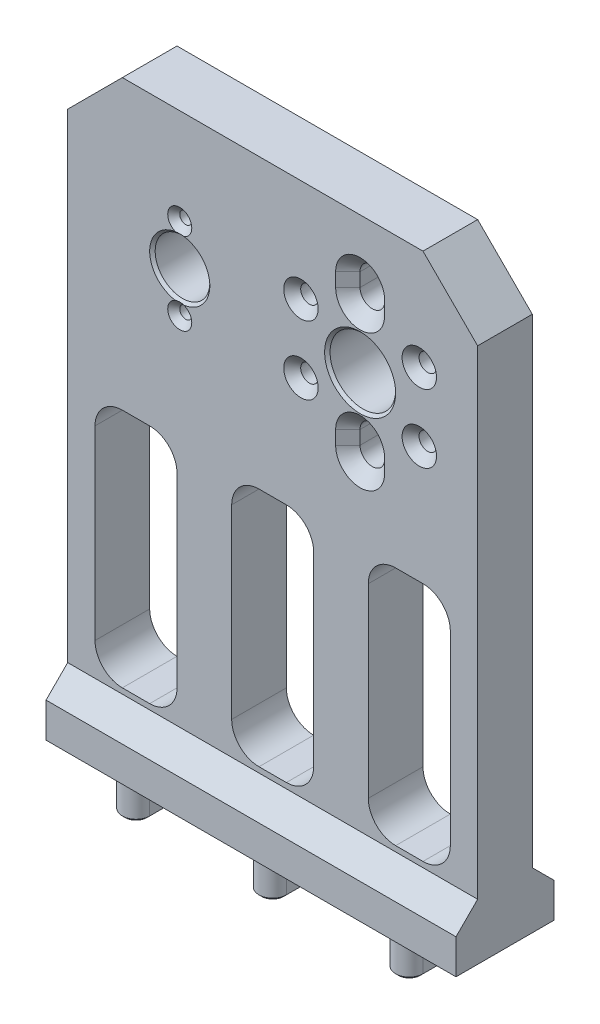
SolidWorks part; units mm, degrees
material "6061 Сплав"
ref_plane "Front Plane" through (0, 0, 0) normal (0, 0, 1) x (1, 0, 0)
ref_plane "Top Plane" through (0, 0, 0) normal (0, 1, 0) x (1, 0, 0)
ref_plane "Right Plane" through (0, 0, 0) normal (1, 0, 0) x (0, 0, -1)
sketch "Sketch1" plane through (0, 0, 0) normal (0, 0, 1) x (1, 0, 0)
  line L0 (59.2007, -25) -> (-71.3111, -25) construction
  line L1 (-37.5, -108) -> (37.5, -108)
  line L2 (-37.5, 0) -> (-37.5, -108)
  line L3 (-37.5, 0) -> (37.5, 0)
  line L4 (37.5, -108) -> (37.5, 0)
  point P6 (0, 0)
  dimension "D1" = 83
  dimension "D2" = 75
  dimension "D3" = 108
extrude "Boss-Extrude1" add sketch "Sketch1" along normal blind 10
sketch "Sketch2" plane through (0, 0, 0) normal (0, 0, 1) x (1, 0, 0)
  line L0 (-37.5, -108) -> (37.5, -108) construction
  line L1 (16, -25) -> (-37.0724, -25) construction
  line L2 (0, 0) -> (0, 29.3343) construction
  line L3 (0, 0) -> (0, -25) construction
  circle A0 centre (16, -25) radius 6
  circle A1 centre (-17, -25) radius 5
  point P2 (0, -108)
  point P7 (0, -25)
  dimension "D1" = 83
  dimension "D2" = 16
  dimension "D3" = 17
extrude "Cut-Extrude2" cut sketch "Sketch2" along normal through all
sketch "Sketch9" plane through (0, 0, 10) normal (0, 0, 1) x (1, 0, 0)
  line L1 (5.1747, -31.25) -> (26.8253, -31.25) construction
  line L2 (5.1747, -31.25) -> (5.1747, -18.75) construction
  line L3 (5.1747, -18.75) -> (26.8253, -18.75) construction
  line L4 (26.8253, -31.25) -> (26.8253, -18.75) construction
  line L5 (5.1747, -31.25) -> (26.8253, -18.75) construction
  line L6 (5.1747, -18.75) -> (26.8253, -31.25) construction
  point P0 (16, -25)
  point P7 (5.1747, -18.75)
  point P8 (26.8253, -18.75)
  point P9 (26.8253, -31.25)
  point P10 (5.1747, -31.25)
  dimension "D1" = 60
hole_wizard "Зенковка для  винта с плоской головкой M31" positions "Sketch11" profile "Sketch10" countersink size "M3" standard "Ansi Metric" end condition through all
sketch "Sketch11" plane through (0, 0, 10) normal (0, 0, 1) x (1, 0, 0)
  point P0 (26.8253, -18.75)
  point P3 (5.1747, -18.75)
  point P6 (5.1747, -31.25)
  point P9 (26.8253, -31.25)
sketch "Sketch10" plane through (26.8253, -18.75, 10) normal (1, 0, 0) x (0, -1, 0)
  line L0 (0, 0) -> (0, 10)
  line L1 (0, 10) -> (1.6, 10)
  line L2 (1.6, 10) -> (1.6, 1.55)
  line L3 (1.6, 1.55) -> (3.15, 0)
  line L5 (3.15, 0) -> (0, 0)
  line L6 (-1.6, 1.55) -> (-3.15, 0) construction
  line L11 (0, -6.35) -> (0, 107.95) construction
  dimension "Thru Hole Dia." = 3.2
  dimension "Thru Hole Depth" = 10
  dimension "Near C'Sink Dia." = 6.3
  dimension "Near C'Sink Angle" = 90
sketch "Sketch13" plane through (37.5, 0, 0) normal (1, 0, 0) x (0, 0, -1)
  line L1 (-10, -108) -> (-10, 0) construction
  line L2 (-10, -97.69) -> (-13.96, -101.65)
  line L3 (-13.96, -101.65) -> (-13.96, -108)
  line L4 (-13.96, -108) -> (-10, -108)
  line L5 (0, -108) -> (0, 0) construction
  line L8 (-10, -97.69) -> (0, -97.69)
  line L10 (3.96, -108) -> (0, -108)
  line L11 (3.96, -101.65) -> (3.96, -108)
  line L12 (0, -97.69) -> (3.96, -101.65)
  line L13 (-10, -108) -> (0, -108)
  point P1 (0, -97.69)
  dimension "D1" = 6.35
  dimension "D2" = 3.96
  dimension "D3" = 3.96
  dimension "D4" = 45
extrude "Boss-Extrude2" add sketch "Sketch13" against normal through all contours L3 L4 L13 L10 L11 L12 L8 L2
sketch "Sketch14" plane through (0, -108, 0) normal (0, -1, 0) x (1, 0, 0)
  line L0 (-37.5, -3.96) -> (37.5, -3.96) construction
  line L1 (-37.5, 13.96) -> (37.5, 13.96) construction
  line L2 (-2.5, 0) -> (-2.5, 10)
  line L3 (25, 13.96) -> (25, -3.96) construction
  line L4 (2.5, 0) -> (2.5, 10)
  line L5 (0, 13.96) -> (0, -3.96) construction
  line L6 (-2.5, 10) -> (2.5, 10) construction
  line L7 (-2.5, 0) -> (2.5, 0) construction
  line L8 (-2.5, 0) -> (2.5, 10) construction
  line L9 (-2.5, 10) -> (2.5, 0) construction
  line L10 (0, -3.96) -> (-37.5, -3.96) construction
  line L11 (22.5, 10) -> (27.5, 10) construction
  line L12 (22.5, 0) -> (22.5, 10)
  line L13 (22.5, 0) -> (27.5, 0) construction
  line L14 (27.5, 0) -> (27.5, 10)
  line L15 (22.5, 0) -> (27.5, 10) construction
  line L16 (22.5, 10) -> (27.5, 0) construction
  line L17 (-27.5, 0) -> (-27.5, 10)
  line L18 (-22.5, 0) -> (-22.5, 10)
  line L19 (-25, 13.96) -> (-25, -3.96) construction
  line L20 (-27.5, 10) -> (-22.5, 10) construction
  line L21 (-27.5, 0) -> (-22.5, 0) construction
  line L22 (25, -3.96) -> (-12.5, -3.96) construction
  line L23 (-27.5, 0) -> (-22.5, 10) construction
  line L24 (-27.5, 10) -> (-22.5, 0) construction
  line L25 (-25, -3.96) -> (-62.5, -3.96) construction
  arc A0 (-2.5, 10) -> (2.5, 10) centre (0, 10) cw
  arc A1 (2.5, 0) -> (-2.5, 0) centre (0, 0) cw
  arc A2 (22.5, 10) -> (27.5, 10) centre (25, 10) cw
  arc A3 (27.5, 0) -> (22.5, 0) centre (25, 0) cw
  arc A4 (-27.5, 10) -> (-22.5, 10) centre (-25, 10) cw
  arc A5 (-22.5, 0) -> (-27.5, 0) centre (-25, 0) cw
  point P11 (25, 5)
  point P12 (0, 5)
  point P13 (0, 13.96)
  point P14 (0, -3.96)
  point P15 (0, 5)
  point P18 (25, 13.96)
  point P19 (25, -3.96)
  point P21 (25, 5)
  point P33 (-25, 5)
  point P34 (-25, 13.96)
  point P35 (-25, -3.96)
  point P36 (-25, 5)
  dimension "D1" = 3
  dimension "D2" = 5
  dimension "D3" = 10
  dimension "D4" = 25
extrude "Boss-Extrude3" add sketch "Sketch14" along normal blind 7
chamfer "Chamfer2" distance 0.5 angle 45 12 edges at (27.5, -115, 5) (25, -115, -2.5) (22.5, -115, 5) (25, -115, 12.5) (-22.5, -115, 5) (-25, -115, -2.5) (-27.5, -115, 5) (-25, -115, 12.5) (2.5, -115, 5) (0, -115, -2.5) (-2.5, -115, 5) (0, -115, 12.5)
sketch "Sketch15" plane through (0, -108, 0) normal (0, -1, 0) x (1, 0, 0)
  line L1 (27.5, 5) -> (0, 5) construction
  line L2 (-27.5, 0) -> (-27.5, 10) construction
  line L3 (27.5, 10) -> (27.5, 0) construction
  line L4 (-37.5, 13.96) -> (-37.5, -3.96) construction
  line L9 (0, 5) -> (-27.5, 5) construction
  line L10 (-27.5, 5) -> (-37.5, 5) construction
  line L12 (27.5, 5) -> (37.5, 5) construction
  line L13 (37.5, 13.96) -> (37.5, -3.96) construction
  point P2 (13.75, 5)
  point P3 (-32.5, 5)
  point P5 (-13.75, 5)
  point P14 (32.5, 5)
sketch "Sketch19" plane through (0, 0, 10) normal (0, 0, 1) x (1, 0, 0)
  circle A0 centre (16, -25) radius 12.5 construction
  point P6 (16, -12.5)
  point P7 (16, -37.5)
  dimension "D1" = 25
hole_wizard "Зенковка для  винта с потайной головкой с внутренним шестигранником M41" positions "Sketch21" profile "Sketch20" size "M4" standard "Ansi Metric" slot yes
sketch "Sketch21" plane through (0, 0, 10) normal (0, 0, 1) x (1, 0, 0)
  line L2 (16, -9) -> (16, -16) construction
  point P0 (16, -12.5)
  point P5 (16, -37.5)
  dimension "D1" = 7
sketch "Sketch20" plane through (16, -12.5, 10) normal (1, 0, 0) x (0, -1, 0)
  line L0 (0, 0) -> (0, 16.3519)
  line L1 (0, 16.3519) -> (2.25, 15)
  line L2 (2.25, 15) -> (2.25, 2.23)
  line L3 (2.25, 2.23) -> (4.48, 0)
  line L5 (4.48, 0) -> (0, 0)
  line L6 (-2.25, 2.23) -> (-4.48, 0) construction
  line L10 (0, 16.3519) -> (-2.25, 15) construction
  line L11 (0, -6.35) -> (0, 107.95) construction
  dimension "Hole Dia." = 4.5
  dimension "Hole Depth" = 15
  dimension "Near C'Sink Dia." = 8.96
  dimension "Near C'Sink Angle" = 90
  dimension "Drill Angle" = 118
chamfer "Chamfer4" distance 0.5 angle 45 16 edges at (22, -25, 10) (6.7747, -31.25, 0) (16, -34, 0) (18.25, -37.5, 0) (13.75, -37.5, 0) (16, -41, 0) (28.4253, -31.25, 0) (28.4253, -18.75, 0) (22, -25, 0) (6.7747, -18.75, 0) (13.75, -12.5, 0) (16, -9, 0) (16, -16, 0) (18.25, -12.5, 0) (-12, -25, 10) (-12, -25, 0)
sketch "Sketch22" plane through (0, 0, 10) normal (0, 0, 1) x (1, 0, 0)
  line L0 (-37.5, -97.69) -> (37.5, -97.69) construction
  line L1 (2.5, -96.69) -> (-2.5, -96.69)
  line L2 (7.5, -91.69) -> (7.5, -57.69)
  line L3 (2.5, -52.69) -> (-2.5, -52.69)
  line L4 (-7.5, -91.69) -> (-7.5, -57.69)
  line L5 (-7.5, -74.69) -> (7.5, -74.69) construction
  line L6 (-22.5, -96.69) -> (-27.5, -96.69)
  line L7 (-17.5, -91.69) -> (-17.5, -57.69)
  line L8 (-22.5, -52.69) -> (-27.5, -52.69)
  line L9 (-32.5, -91.69) -> (-32.5, -57.69)
  line L10 (-32.5, -74.69) -> (-17.5, -74.69) construction
  line L11 (27.5, -96.69) -> (22.5, -96.69)
  line L12 (32.5, -91.69) -> (32.5, -57.69)
  line L13 (27.5, -52.69) -> (22.5, -52.69)
  line L14 (17.5, -91.69) -> (17.5, -57.69)
  line L19 (17.5, -74.69) -> (32.5, -74.69) construction
  arc A0 (-2.5, -96.69) -> (-7.5, -91.69) centre (-2.5, -91.69) cw
  arc A1 (2.5, -96.69) -> (7.5, -91.69) centre (2.5, -91.69) ccw
  arc A2 (22.5, -96.69) -> (17.5, -91.69) centre (22.5, -91.69) cw
  arc A3 (27.5, -96.69) -> (32.5, -91.69) centre (27.5, -91.69) ccw
  arc A4 (32.5, -57.69) -> (27.5, -52.69) centre (27.5, -57.69) ccw
  arc A5 (22.5, -52.69) -> (17.5, -57.69) centre (22.5, -57.69) ccw
  arc A6 (7.5, -57.69) -> (2.5, -52.69) centre (2.5, -57.69) ccw
  arc A7 (-2.5, -52.69) -> (-7.5, -57.69) centre (-2.5, -57.69) ccw
  arc A8 (-27.5, -96.69) -> (-32.5, -91.69) centre (-27.5, -91.69) cw
  arc A9 (-22.5, -96.69) -> (-17.5, -91.69) centre (-22.5, -91.69) ccw
  arc A10 (-17.5, -57.69) -> (-22.5, -52.69) centre (-22.5, -57.69) ccw
  arc A11 (-27.5, -52.69) -> (-32.5, -57.69) centre (-27.5, -57.69) ccw
  point P4 (0, -74.69)
  point P18 (25, -74.69)
  point P24 (-25, -74.69)
  dimension "D1" = 3
  dimension "D2" = 25
  dimension "D5" = 5
  dimension "D3" = 5
  dimension "D4" = 34
  dimension "D6" = 1
extrude "Cut-Extrude3" cut sketch "Sketch22" against normal through all
chamfer "Chamfer5" [suppressed] distance 0.5 angle 45
sketch "Sketch24" plane through (0, 0, 10) normal (0, 0, 1) x (1, 0, 0)
  line L0 (-17, -25) -> (-17, -17.5) construction
  line L1 (-17, -25) -> (-17, -32.5) construction
  point P5 (-17, -17.5)
  point P6 (-17, -32.5)
  dimension "D1" = 15
hole_wizard "CSK for M2 Flat Head Machine Screw1" positions "Sketch26" profile "Sketch27" countersink size "M2" standard "ANSI Metric" end condition through all
sketch "Sketch26" plane through (0, 0, 10) normal (0, 0, 1) x (1, 0, 0)
  point P0 (-17, -17.5)
  point P3 (-17, -32.5)
sketch "Sketch27" plane through (-17, -17.5, 10) normal (1, 0, 0) x (0, -1, 0)
  line L0 (0, 0) -> (0, 13.96)
  line L1 (0, 13.96) -> (1.1, 13.96)
  line L2 (1.1, 13.96) -> (1.1, 1.1)
  line L3 (1.1, 1.1) -> (2.2, 0)
  line L5 (2.2, 0) -> (0, 0)
  line L6 (-1.1, 1.1) -> (-2.2, 0) construction
  line L11 (0, -6.35) -> (0, 107.95) construction
  dimension "Thru Hole Dia." = 2.2
  dimension "Thru Hole Depth" = 13.96
  dimension "Near C'Sink Dia." = 4.4
  dimension "Near C'Sink Angle" = 90
hole_wizard "M5x0.8 Tapped Hole1" positions "Sketch29" profile "Sketch30" tap size "M5x0.8" standard "ANSI Metric"
sketch "Sketch29" plane through (0, -108, 0) normal (0, -1, 0) x (-1, 0, 0)
  point P0 (32.5, -5)
  point P3 (13.75, -5)
  point P6 (-13.75, -5)
  point P9 (-32.5, -5)
sketch "Sketch30" plane through (-32.5, -108, 5) normal (1, 0, 0) x (0, 0, -1)
  line L0 (0, 0) -> (0, 11.6618)
  line L1 (0, 11.6618) -> (2.1, 10.4)
  line L2 (2.1, 10.4) -> (2.1, 0)
  line L5 (2.1, 0) -> (0, 0)
  line L10 (0, 11.6618) -> (-2.1, 10.4) construction
  line L11 (0, -6.35) -> (0, 107.95) construction
  dimension "Tap Drill Dia." = 4.2
  dimension "Tap Drill Depth" = 10.4
  dimension "Drill Angle" = 118
cosmetic thread "Hole Thread1" parameters "D1"=8, "D2"=5
cosmetic thread "Hole Thread2" parameters "D1"=8, "D2"=5
cosmetic thread "Hole Thread3" parameters "D1"=8, "D2"=5
cosmetic thread "Отверстие резьбы2" parameters "D1"=8, "D2"=5
chamfer "Chamfer6" distance 10 angle 45 2 edges at (-37.5, 0, 5) (37.5, 0, 5)
